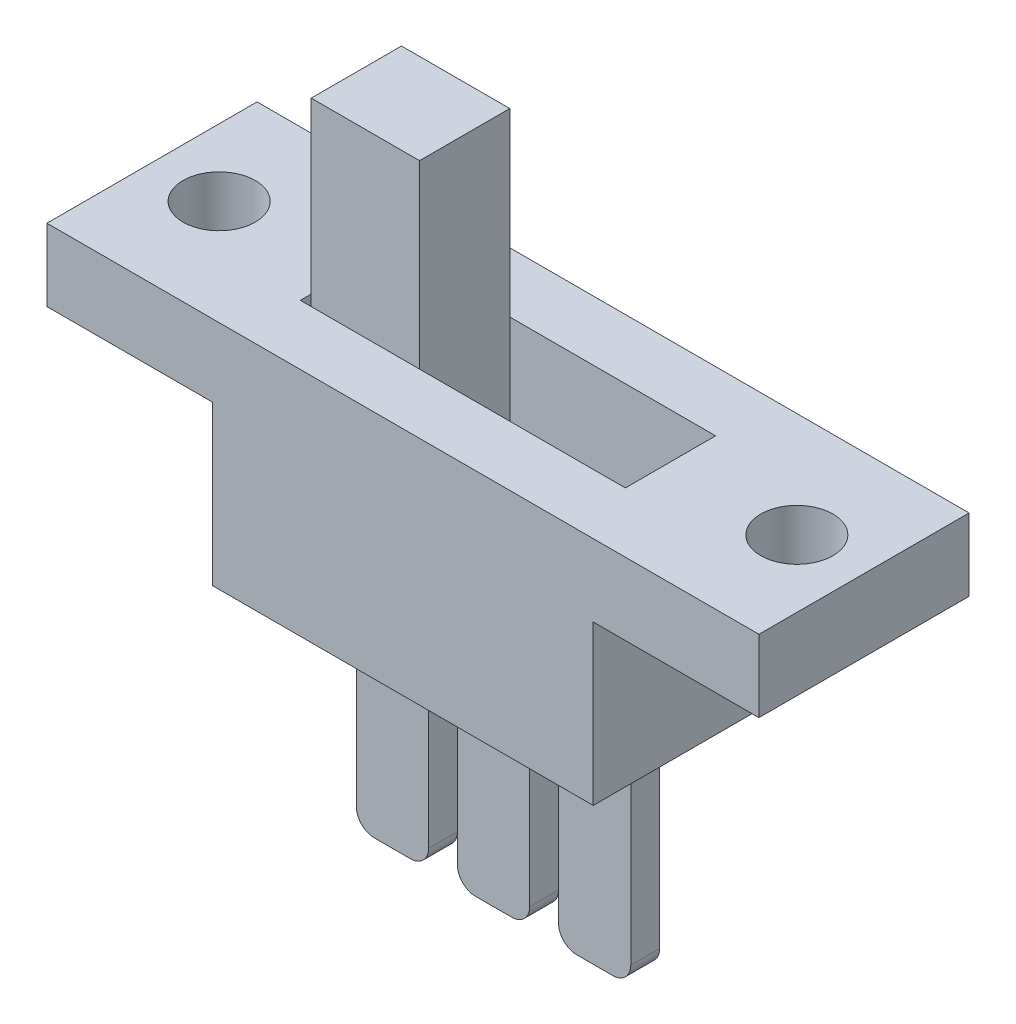
SolidWorks part; units mm, degrees
ref_plane "Front Plane" through (0, 0, 0) normal (0, 0, 1) x (1, 0, 0)
ref_plane "Top Plane" through (0, 0, 0) normal (0, 1, 0) x (1, 0, 0)
ref_plane "Right Plane" through (0, 0, 0) normal (1, 0, 0) x (0, 0, -1)
sketch "Sketch1" plane through (0, 0, 0) normal (0, 1, 0) x (1, 0, 0)
  line L0 (-8, 0) -> (8, 0) construction
  line L1 (-9.86, 2.91) -> (9.86, 2.91)
  line L2 (-9.86, 2.91) -> (-9.86, -2.91)
  line L3 (-9.86, -2.91) -> (9.86, -2.91)
  line L4 (9.86, 2.91) -> (9.86, -2.91)
  line L5 (-9.86, 2.91) -> (9.86, -2.91) construction
  line L6 (-9.86, -2.91) -> (9.86, 2.91) construction
  line L8 (-4.5, 1.25) -> (4.5, 1.25)
  line L9 (-4.5, 1.25) -> (-4.5, -1.25)
  line L10 (-4.5, -1.25) -> (4.5, -1.25)
  line L11 (4.5, 1.25) -> (4.5, -1.25)
  line L12 (-4.5, 1.25) -> (4.5, -1.25) construction
  line L13 (-4.5, -1.25) -> (4.5, 1.25) construction
  line L14 (-4.2, 1.25) -> (-1.2, 1.25)
  line L15 (-4.2, 1.25) -> (-4.2, -1.25)
  line L16 (-4.2, -1.25) -> (-1.2, -1.25)
  line L17 (-1.2, 1.25) -> (-1.2, -1.25)
  line L18 (-5.27, 2.91) -> (5.27, 2.91)
  line L19 (-5.27, 2.91) -> (-5.27, -2.91)
  line L20 (-5.27, -2.91) -> (5.27, -2.91)
  line L21 (5.27, 2.91) -> (5.27, -2.91)
  line L22 (-5.27, 2.91) -> (5.27, -2.91) construction
  line L23 (-5.27, -2.91) -> (5.27, 2.91) construction
  circle A0 centre (8, 0) radius 1
  circle A1 centre (-8, 0) radius 1
  point P0 (0, 0)
  point P10 (0, 0)
  point P11 (0, 0)
  point P20 (0, 0)
  dimension "D1" = 2
  dimension "D2" = 2
  dimension "D3" = 19.72
  dimension "D4" = 16
  dimension "D5" = 5.82
  dimension "D6" = 2.5
  dimension "D7" = 9
  dimension "D8" = 3
  dimension "D9" = 0.3
  dimension "D10" = 10.54
extrude "Boss-Extrude1" add sketch "Sketch1" along normal blind 2 contours A1 | A0 | L3 L4 L1 L2 region at (8, 0, 0) region at (-8, 0, 0)
extrude "Boss-Extrude2" add sketch "Sketch1<3>" against normal blind 4.4 contours L21 L1 L19 L3 L8 L11 L10 L9 | L10 L11 L8 L9 region at (0, 0, -2.7896)
sketch "Sketch1<3>" plane through (0, 0, 0) normal (0, 1, 0) x (1, 0, 0) same geometry as "Sketch1"
extrude "Cut-Extrude1" cut sketch "Sketch1<4>" against normal blind 3 and the other way through all contours L8 L11 L10 L9
sketch "Sketch1<4>" plane through (0, 0, 0) normal (0, 1, 0) x (1, 0, 0) same geometry as "Sketch1"
extrude "Boss-Extrude3" add sketch "Sketch1<5>" along normal up to surface (2 mm away) from surface contours L17 L16 L15 L14 up to face at (-8, 2, 1) starting at face at (0, -3, 0)
sketch "Sketch1<5>" plane through (0, 0, 0) normal (0, 1, 0) x (1, 0, 0) same geometry as "Sketch1"
extrude "Boss-Extrude4" add sketch "Sketch1<6>" along normal blind 5 from surface contours L17 L16 L15 L14 starting at face at (1.65, 2, 0)
sketch "Sketch1<6>" plane through (0, 0, 0) normal (0, 1, 0) x (1, 0, 0) same geometry as "Sketch1"
sketch "Sketch2" plane through (0, 0, 0) normal (0, 1, 0) x (1, 0, 0)
  line L0 (-1.8, 0.4) -> (-1.8, -0.4)
  line L1 (-3.8, 0.4) -> (3.8, 0.4)
  line L2 (-3.8, 0.4) -> (-3.8, -0.4)
  line L3 (-3.8, -0.4) -> (3.8, -0.4)
  line L4 (3.8, 0.4) -> (3.8, -0.4)
  line L5 (-3.8, 0.4) -> (3.8, -0.4) construction
  line L6 (-3.8, -0.4) -> (3.8, 0.4) construction
  line L7 (-1, 0.4) -> (-1, -0.4)
  line L8 (1.8, 0.4) -> (1.8, -0.4)
  line L9 (1, 0.4) -> (1, -0.4)
  point P0 (0, 0)
  point P14 (3.8, 0)
  point P15 (-1, 0)
  dimension "D1" = 0.8
  dimension "D2" = 7.6
  dimension "D3" = 2
  dimension "D4" = 2
  dimension "D5" = 2
  dimension "D6" = 0.8
extrude "Boss-Extrude5" add sketch "Sketch2" against normal blind 6.32 from surface contours L2 L3 L0 L1 | L9 L1 L7 L3 | L1 L8 L3 L4 region at (-2.8, 0, 0) region at (0, 0, 0) region at (2.8, 0, 0) starting at face at (0, -4.4, 0)
fillet "Fillet1" radius 0.5 6 edges at (-3.8, -10.72, 0) (-1.8, -10.72, 0) (-1, -10.72, 0) (1, -10.72, 0) (1.8, -10.72, 0) (3.8, -10.72, 0)
sketch "Sketch3" plane through (0, 0, 0) normal (0, 1, 0) x (1, 0, 0)
  line L0 (-8, 0) -> (-8, -6) construction
  circle A0 centre (-8, -6) radius 1.2 construction
  dimension "D2" = 2.4
  dimension "D1" = 6
